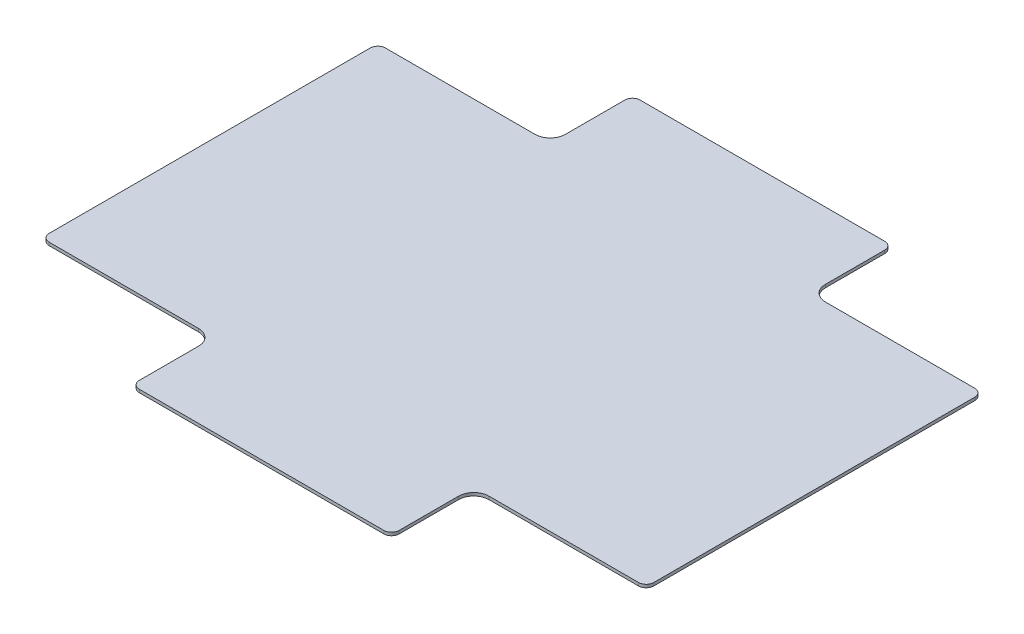
SolidWorks part; units mm, degrees
material "7075-T6, Пластина (SS)"
ref_plane "Спереди" through (0, 0, 0) normal (0, 0, 1) x (1, 0, 0)
ref_plane "Сверху" through (0, 0, 0) normal (0, 1, 0) x (1, 0, 0)
ref_plane "Справа" through (0, 0, 0) normal (1, 0, 0) x (0, 0, -1)
sketch "Эскиз1" plane through (0, 0, 0) normal (0, 1, 0) x (1, 0, 0)
  line L1 (-80, -163.8055) -> (80, -163.8055)
  line L2 (-197.7687, -105) -> (-197.7687, 105)
  line L3 (-80, 163.8055) -> (80, 163.8055)
  line L4 (197.7687, -105) -> (197.7687, 105)
  line L5 (-236.4266, 144.4996) -> (-147.9018, 144.4996) construction
  line L6 (-147.9018, 144.4996) -> (286.4952, 144.4996) construction
  line L18 (-284.5497, 0) -> (284.3305, 0) construction
  line L19 (-160.9018, 110) -> (-134.9018, 110)
  line L20 (-160.9018, 110) -> (-160.9018, 0)
  line L21 (-160.9018, 0) -> (-134.9018, 0)
  line L22 (-134.9018, 110) -> (-134.9018, 0)
  line L23 (-147.9018, -182.6295) -> (-147.9018, 219.9923) construction
  line L24 (-160.9018, 0) -> (-134.9018, 0)
  line L25 (-160.9018, 0) -> (-160.9018, -110)
  line L26 (-160.9018, -110) -> (-134.9018, -110)
  line L27 (-134.9018, 0) -> (-134.9018, -110)
  line L28 (-97.9018, -119.4996) -> (-197.9018, -119.4996)
  line L29 (-97.9018, 169.4996) -> (-197.9018, 169.4996)
  line L30 (-97.9018, 169.4996) -> (-97.9018, 119.4996)
  line L31 (-97.9018, 119.4996) -> (-197.9018, 119.4996)
  line L32 (-197.9018, 169.4996) -> (-197.9018, 119.4996)
  line L33 (-97.9018, 169.4996) -> (-197.9018, 119.4996) construction
  line L34 (-97.9018, 119.4996) -> (-197.9018, 169.4996) construction
  line L35 (-197.9018, -169.4996) -> (-197.9018, -119.4996)
  line L36 (-97.9018, -169.4996) -> (-197.9018, -169.4996)
  line L37 (-97.9018, -169.4996) -> (-97.9018, -119.4996)
  line L39 (-85, 120) -> (-85, 158.8055)
  line L40 (0, 262.7398) -> (0, -186.5795) construction
  line L41 (-192.7687, 110) -> (-95, 110)
  line L43 (-192.7687, -110) -> (-95, -110)
  line L44 (-85, -120) -> (-85, -158.8055)
  line L45 (85, 120) -> (85, 158.8055)
  line L46 (192.7687, 110) -> (95, 110)
  line L47 (192.7687, -110) -> (95, -110)
  line L48 (85, -120) -> (85, -158.8055)
  line L49 (97.9018, -169.4996) -> (97.9018, -119.4996)
  line L50 (97.9018, -169.4996) -> (197.9018, -169.4996)
  line L51 (197.9018, -169.4996) -> (197.9018, -119.4996)
  line L52 (97.9018, -119.4996) -> (197.9018, -119.4996)
  line L53 (160.9018, 0) -> (160.9018, -110)
  line L54 (160.9018, -110) -> (134.9018, -110)
  line L55 (134.9018, 0) -> (134.9018, -110)
  line L56 (160.9018, 0) -> (134.9018, 0)
  line L57 (160.9018, 110) -> (160.9018, 0)
  line L58 (160.9018, 0) -> (134.9018, 0)
  line L59 (134.9018, 110) -> (134.9018, 0)
  line L60 (160.9018, 110) -> (134.9018, 110)
  line L61 (97.9018, 119.4996) -> (197.9018, 119.4996)
  line L62 (197.9018, 169.4996) -> (197.9018, 119.4996)
  line L63 (97.9018, 169.4996) -> (197.9018, 169.4996)
  line L64 (97.9018, 169.4996) -> (97.9018, 119.4996)
  arc A0 (85, -120) -> (95, -110) centre (95, -120) cw
  arc A1 (85, 120) -> (95, 110) centre (95, 120) ccw
  arc A2 (-95, -110) -> (-85, -120) centre (-95, -120) cw
  arc A3 (-85, 120) -> (-95, 110) centre (-95, 120) cw
  arc A4 (192.7687, -110) -> (197.7687, -105) centre (192.7687, -105) ccw
  arc A5 (85, -158.8055) -> (80, -163.8055) centre (80, -158.8055) cw
  arc A6 (-85, -158.8055) -> (-80, -163.8055) centre (-80, -158.8055) ccw
  arc A7 (-192.7687, -110) -> (-197.7687, -105) centre (-192.7687, -105) cw
  arc A8 (-192.7687, 110) -> (-197.7687, 105) centre (-192.7687, 105) ccw
  arc A9 (197.7687, 105) -> (192.7687, 110) centre (192.7687, 105) ccw
  arc A10 (85, 158.8055) -> (80, 163.8055) centre (80, 158.8055) ccw
  arc A11 (-85, 158.8055) -> (-80, 163.8055) centre (-80, 158.8055) cw
  point P0 (0, 0)
  point P3 (85, -110)
  point P17 (-147.9018, 110)
  point P18 (-147.9018, 110)
  point P20 (-147.9018, 0)
  point P22 (-150, 134)
  point P37 (-147.9018, 144.4996)
  point P46 (85, 110)
  point P52 (-85, -110)
  point P55 (-85, 110)
  point P56 (-147.9018, 0)
  point P77 (197.7687, -110)
  point P80 (85, -163.8055)
  point P83 (-85, -163.8055)
  point P86 (-197.7687, -110)
  point P89 (-197.7687, 110)
  point P92 (197.7687, 110)
  point P95 (85, 163.8055)
  point P98 (-85, 163.8055)
  dimension "D2" = 50
  dimension "D6" = 10
  dimension "D4" = 5
  dimension "D3" = 26
  dimension "D5" = 338.9991
  dimension "D7" = 395.5373
  dimension "D8" = 110
  dimension "D9" = 170
  dimension "D10" = 100
  dimension "D13" = 9.4996
  dimension "D14" = 12.9018
sketch "Эскиз2" plane through (0, 0, 0) normal (0, 1, 0) x (1, 0, 0)
  line L0 (-162.9105, 114) -> (-136.9105, 114)
  line L1 (-162.9105, 114) -> (-162.9105, 0)
  line L2 (-162.9105, 0) -> (-136.9105, 0)
  line L3 (-136.9105, 114) -> (-136.9105, 0)
  line L4 (-149.9105, -192.6295) -> (-149.9105, 209.9923) construction
  line L5 (-162.9105, 0) -> (-136.9105, 0)
  line L6 (-162.9105, 0) -> (-162.9105, -114)
  line L7 (-162.9105, -114) -> (-136.9105, -114)
  line L8 (-136.9105, 0) -> (-136.9105, -114)
  line L9 (-99.9105, -123.5568) -> (-199.9105, -123.5568)
  line L10 (-99.9105, 163.4996) -> (-199.9105, 163.4996)
  line L11 (-99.9105, 163.4996) -> (-99.9105, 123.4996)
  line L12 (-99.9105, 123.4996) -> (-199.9105, 123.4996)
  line L13 (-199.9105, 163.4996) -> (-199.9105, 123.4996)
  line L14 (-199.9105, -163.5568) -> (-199.9105, -123.5568)
  line L15 (-99.9105, -163.5568) -> (-199.9105, -163.5568)
  line L16 (-99.9105, -163.5568) -> (-99.9105, -123.5568)
  line L17 (-284.5497, 0) -> (284.3305, 0) construction
  point P11 (-149.9105, 0)
  point P12 (-149.9105, 0)
sketch "Эскиз3" plane through (0, 0, 0) normal (0, 1, 0) x (1, 0, 0)
  line L0 (-89.8176, -177.9027) -> (70.2405, -177.9027)
  line L1 (-209.7886, -106.9112) -> (-209.7886, 106.8353)
  line L2 (-80.029, 172.0973) -> (50.2405, 172.0973)
  line L3 (170.2114, -106.9112) -> (170.2114, 103.9123)
  line L4 (-87.1938, 124.0033) -> (-87.1938, 164.9326)
  line L5 (-202.6239, 114) -> (-97.1971, 114)
  line L6 (-202.6239, -114.076) -> (-106.9857, -114.076)
  line L7 (-96.9823, -124.0793) -> (-96.9823, -170.738)
  line L8 (57.4052, 121.0803) -> (57.4052, 164.9326)
  line L9 (163.0467, 111.077) -> (67.4085, 111.077)
  line L10 (163.0467, -114.076) -> (87.4085, -114.076)
  line L11 (77.4052, -124.0793) -> (77.4052, -170.738)
  line L13 (-162.9105, 114) -> (-136.9105, 114) construction
  arc A0 (77.4052, -124.0793) -> (87.4085, -114.076) centre (87.4085, -124.0793) cw
  arc A1 (57.4052, 121.0803) -> (67.4085, 111.077) centre (67.4085, 121.0803) ccw
  arc A2 (-106.9857, -114.076) -> (-96.9823, -124.0793) centre (-106.9857, -124.0793) cw
  arc A3 (-87.1938, 124.0033) -> (-97.1971, 114) centre (-97.1971, 124.0033) cw
  arc A4 (-80.029, 172.0973) -> (-87.1938, 164.9326) centre (-80.029, 164.9326) ccw
  arc A5 (50.2405, 172.0973) -> (57.4052, 164.9326) centre (50.2405, 164.9326) cw
  arc A6 (170.2114, 103.9123) -> (163.0467, 111.077) centre (163.0467, 103.9123) ccw
  arc A7 (170.2114, -106.9112) -> (163.0467, -114.076) centre (163.0467, -106.9112) cw
  arc A8 (70.2405, -177.9027) -> (77.4052, -170.738) centre (70.2405, -170.738) ccw
  arc A9 (-89.8176, -177.9027) -> (-96.9823, -170.738) centre (-89.8176, -170.738) cw
  arc A10 (-209.7886, -106.9112) -> (-202.6239, -114.076) centre (-202.6239, -106.9112) ccw
  arc A11 (-209.7886, 106.8353) -> (-202.6239, 114) centre (-202.6239, 106.8353) cw
  point P36 (115.2276, 111.077)
  point P39 (-149.9105, 114)
  point P42 (-149.9105, 114)
  dimension "D3" = 10.0033
  dimension "D4" = 7.1647
  dimension "D1" = 380
  dimension "D2" = 350
  dimension "D5" = 112.8062
  dimension "D6" = 63.8267
  dimension "D7" = 61.0203
extrude "Бобышка-Вытянуть1" add sketch "Эскиз1" along normal blind 2 separate body contours A11 L39 A3 L41 L22 L27 L43 A2 L44 A6 L1 A5 L48 A0 L47 L55 L59 L46 A1 L45 A10 L3 | L4 A9 L46 L57 L53 L47 A4 | L46 L59 L56 L57 | L53 L56 L55 L47 | L27 L21 L25 L26 | L41 A8 L2 A7 L43 L25 L20 | L22 L19 L20 L21 region at (0, 0, 0) region at (-147.9018, 0, 55) region at (147.9018, 0, 55) region at (-179.3123, 0, 0) region at (-147.9018, 0, -55) region at (179.3123, 0, 0) region at (147.9018, 0, -55)
